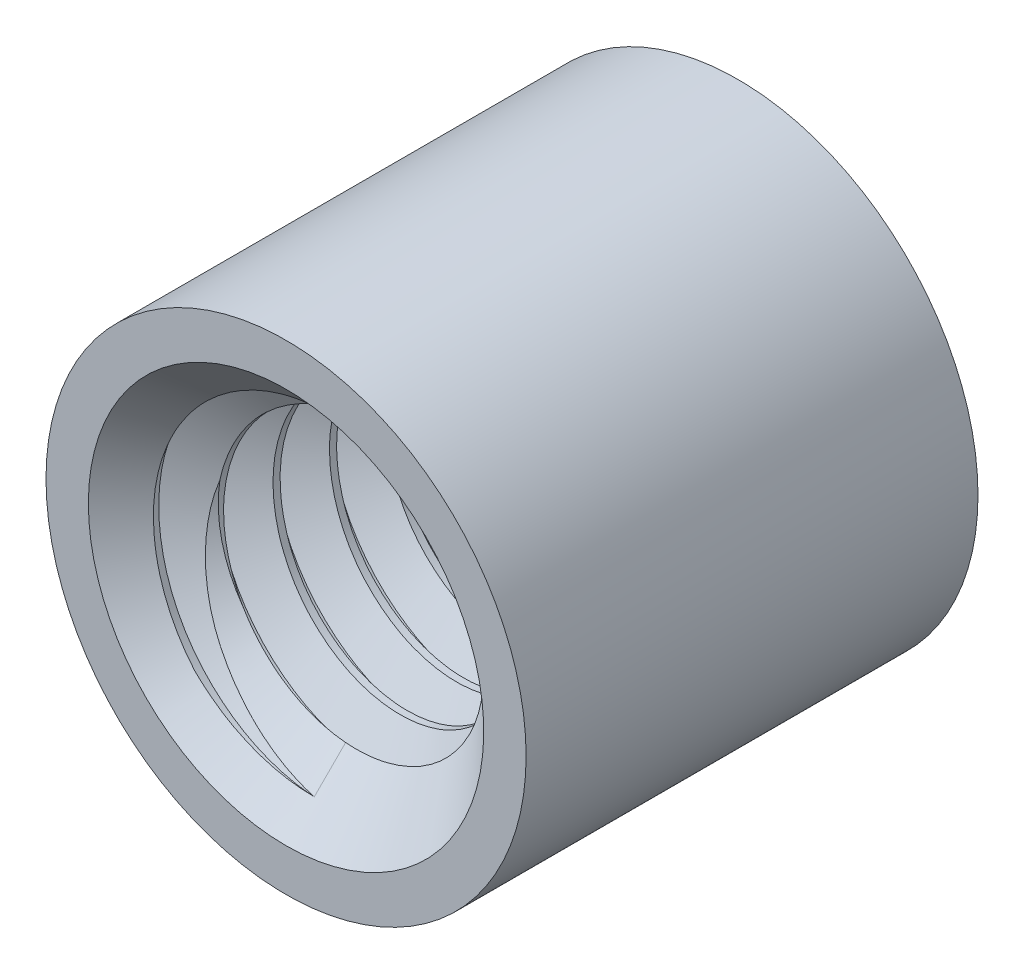
SolidWorks part; units mm, degrees
ref_plane "Front Plane" through (0, 0, 0) normal (0, 0, 1) x (1, 0, 0)
ref_plane "Top Plane" through (0, 0, 0) normal (0, 1, 0) x (1, 0, 0)
ref_plane "Right Plane" through (0, 0, 0) normal (1, 0, 0) x (0, 0, -1)
sketch "SK_T1_tube" plane through (0, 0, 0) normal (0, 1, 0) x (1, 0, 0)
  line L0 (3.7314, 17.272) -> (6.7469, 17.272)
  line L1 (6.7469, 17.272) -> (6.7469, 4.572)
  line L2 (6.7469, 4.572) -> (3.7314, 4.572)
  line L3 (3.7314, 4.572) -> (3.7314, 17.272)
  line L4 (0, 50.8) -> (0, -50.8) construction
revolve "T1_Tube" add sketch "SK_T1_tube" angle 360 about L4
ref_plane "Z=-0.69172" through (0, 0, -17.5696) normal (0, 0, 1) x (1, 0, 0)
sketch "SK_T2_helixbase" plane through (0, 0, -17.5696) normal (0, 0, 1) x (1, 0, 0)
  circle A0 centre (0, 0) radius 4.7625
curve "T2_Helix" pitch 1.5875 height 14.2875 radius 4.7625 centre (0, 0, -17.5696) axis (0, 0, 1) start towards (1, 0, 0)
sketch "SK_T3_groove" plane through (0, 0, 0) normal (0, 1, 0) x (1, 0, 0)
  line L0 (3.3504, 18.2642) -> (3.7314, 18.2642)
  line L1 (3.7314, 18.2642) -> (4.7625, 17.6689)
  line L2 (4.7625, 17.6689) -> (4.7625, 17.4704)
  line L3 (4.7625, 17.4704) -> (3.7314, 16.8751)
  line L4 (3.7314, 16.8751) -> (3.3504, 16.8751)
  line L5 (3.3504, 16.8751) -> (3.3504, 18.2642)
sweep "T3_ThreadSweepCut" cut profiles "SK_T3_groove" path "T2_Helix" align with end faces yes
sketch "SK_T4_csk" plane through (0, 0, 0) normal (0, 1, 0) x (1, 0, 0)
  line L0 (0, 17.78) -> (6.0642, 17.78)
  line L1 (6.0642, 17.78) -> (3.302, 15.0178)
  line L2 (3.302, 15.0178) -> (0, 15.0178)
  line L3 (0, 15.0178) -> (0, 17.78)
  line L4 (0, 4.064) -> (6.0642, 4.064)
  line L5 (6.0642, 4.064) -> (3.302, 6.8262)
  line L6 (3.302, 6.8262) -> (0, 6.8262)
  line L7 (0, 6.8262) -> (0, 4.064)
  line L8 (0, 50.8) -> (0, -50.8) construction
revolve "T4_Countersinks" cut sketch "SK_T4_csk" angle 360 about L8
equation "\"R_insert_out\" = 0.265625in"
equation "\"Z_insert_bot\" = -0.680000in"
equation "\"Z_insert_top\" = -0.180000in"
equation "\"Pitch\" = 0.062500in"
equation "\"R_major\" = 0.187500in"
equation "\"R_minor\" = 0.146906in"
equation "\"Flat\" = 0.007812in"
equation "\"Flank_run\" = 0.023438in"
equation "\"Z_root_phase\" = -0.379218in"
equation "\"N_turns\" = 9.000000"
equation "\"R_csk\" = 0.218750in"
equation "\"Csk_depth\" = 0.031250in"
equation "\"csk_angle_deg\" = 90.000000"
